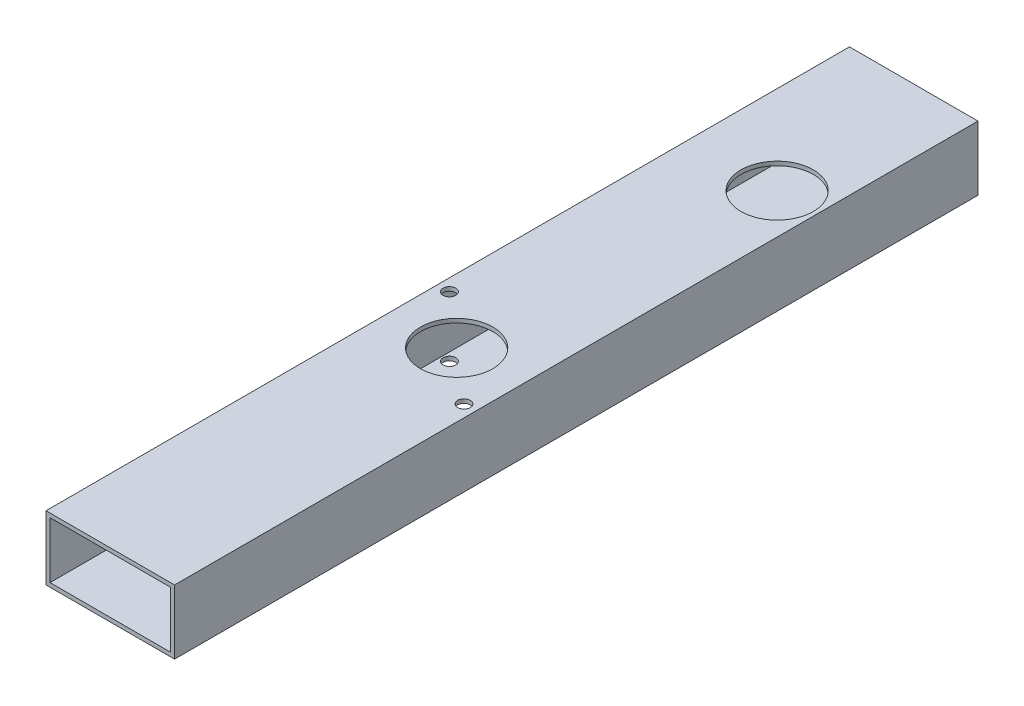
SolidWorks part; units mm, degrees
material "6061 Alloy"
ref_plane "Front Plane" through (0, 0, 0) normal (0, 0, 1) x (1, 0, 0)
ref_plane "Top Plane" through (0, 0, 0) normal (0, 1, 0) x (1, 0, 0)
ref_plane "Right Plane" through (0, 0, 0) normal (1, 0, 0) x (0, 0, -1)
sketch "Sketch1" plane through (0, 0, 0) normal (0, 0, 1) x (1, 0, 0)
  line L0 (-23.8125, 11.1125) -> (23.8125, 11.1125)
  line L2 (-25.4, 12.7) -> (25.4, 12.7)
  line L3 (-25.4, 12.7) -> (-25.4, -12.7)
  line L4 (-25.4, -12.7) -> (25.4, -12.7)
  line L5 (25.4, 12.7) -> (25.4, -12.7)
  line L10 (23.8125, 11.1125) -> (23.8125, -11.1125)
  line L11 (-23.8125, -11.1125) -> (23.8125, -11.1125)
  line L12 (-23.8125, 11.1125) -> (-23.8125, -11.1125)
  point P12 (0, 12.7)
  point P14 (25.4, 0)
  dimension "Wall Thickness" = 1.5875
  dimension "Outside Width" = 50.8
  dimension "Outside Height" = 25.4
  dimension "Inside Height" = 22.225
  dimension "Inside Width" = 47.625
sketch "Sketch2" plane through (0, 0, 0) normal (1, 0, 0) x (0, 0, -1)
  line L0 (158.75, 0) -> (-158.75, 0)
  point P4 (0, 0)
  point P7 (-158.75, 0)
  point P10 (158.75, 0)
  dimension "Length" = 317.5
sketch "Sketch3" plane through (0, 0, 0) normal (0, 0, 1) x (1, 0, 0)
  line L21 (25.4, 12.7) -> (-25.4, 12.7)
  line L22 (25.4, -12.7) -> (25.4, 12.7)
  line L23 (-25.4, -12.7) -> (25.4, -12.7)
  line L24 (-25.4, 12.7) -> (-25.4, -12.7)
  line L25 (25.4, 12.7) -> (-25.4, 12.7)
  line L26 (25.4, -12.7) -> (25.4, 12.7)
  line L27 (-25.4, -12.7) -> (25.4, -12.7)
  line L28 (-25.4, 12.7) -> (-25.4, -12.7)
  line L29 (23.8125, 11.1125) -> (-23.8125, 11.1125)
  line L30 (23.8125, -11.1125) -> (23.8125, 11.1125)
  line L31 (-23.8125, -11.1125) -> (23.8125, -11.1125)
  line L32 (-23.8125, 11.1125) -> (-23.8125, -11.1125)
  line L33 (23.8125, 11.1125) -> (-23.8125, 11.1125)
  line L34 (23.8125, -11.1125) -> (23.8125, 11.1125)
  line L35 (-23.8125, -11.1125) -> (23.8125, -11.1125)
  line L36 (-23.8125, 11.1125) -> (-23.8125, -11.1125)
  dimension "D1" = 0
  dimension "D2" = 0
extrude "Boss-Extrude1" add sketch "Sketch3" along normal up to vertex (158.75 mm away) and the other way up to vertex (158.75 mm away) up to point (0, 0, 158.75) other way up to point (0, 0, -158.75)
sketch "Drawing Reference" plane through (0, 0, 0) normal (1, 0, 0) x (0, 0, -1)
  line L0 (-158.75, 0) -> (158.75, 0) construction
  line L1 (0, -12.7) -> (0, 12.7) construction
  line L2 (-158.75, -12.7) -> (158.75, -12.7) construction
  line L5 (-158.75, 12.7) -> (158.75, 12.7) construction
  point P7 (-122.174, 0)
  point P8 (122.174, 0)
  dimension "D1" = 36.576
sketch "Sketch4" plane through (0, 12.7, 0) normal (0, 1, 0) x (1, 0, 0)
  line L0 (0, 158.75) -> (0, 95.25) construction
  line L1 (25.4, 158.75) -> (-25.4, 158.75) construction
  line L2 (0, 95.25) -> (9.525, 95.25) construction
  line L3 (0, 158.75) -> (0, -26.67) construction
  circle A1 centre (9.525, 95.25) radius 14.2875
  circle A3 centre (9.525, 95.25) radius 117.5004 construction
  circle A4 centre (0, -21.8637) radius 14.2875
  dimension "D1" = 63.5
  dimension "D3" = 235.0008
  dimension "D2" = 9.525
extrude "Cut-Extrude1" cut sketch "Sketch4" against normal blind 39.37
sketch "Sketch6" plane through (0, 12.7, 0) normal (0, 1, 0) x (1, 0, 0)
  line L0 (-20.6308, -4.1018) -> (20.6308, -39.6256) construction
  circle A0 centre (0, -21.8637) radius 27.2234 construction
  point P8 (0, -21.8637)
hole_wizard "#10 Clearance Hole1" positions "Sketch7" profile "Sketch8" hole size "#10" standard "ANSI Inch" end condition through all
sketch "Sketch7" plane through (0, 12.7, 0) normal (0, 1, 0) x (1, 0, 0)
  point P0 (-20.6308, -4.1018)
  point P3 (20.6308, -39.6256)
sketch "Sketch8" plane through (-20.6308, 12.7, 4.1018) normal (1, 0, 0) x (0, 0, 1)
  line L0 (0, 0) -> (0, 25.4)
  line L1 (0, 25.4) -> (2.4892, 25.4)
  line L2 (2.4892, 25.4) -> (2.4892, 0)
  line L5 (2.4892, 0) -> (0, 0)
  line L11 (0, -6.35) -> (0, 107.95) construction
  dimension "Thru Hole Dia." = 4.9784
  dimension "Thru Hole Depth" = 25.4
equation "\"D1@Drawing Reference\"=\"Outside Width@Sketch1\" * 0.72"
